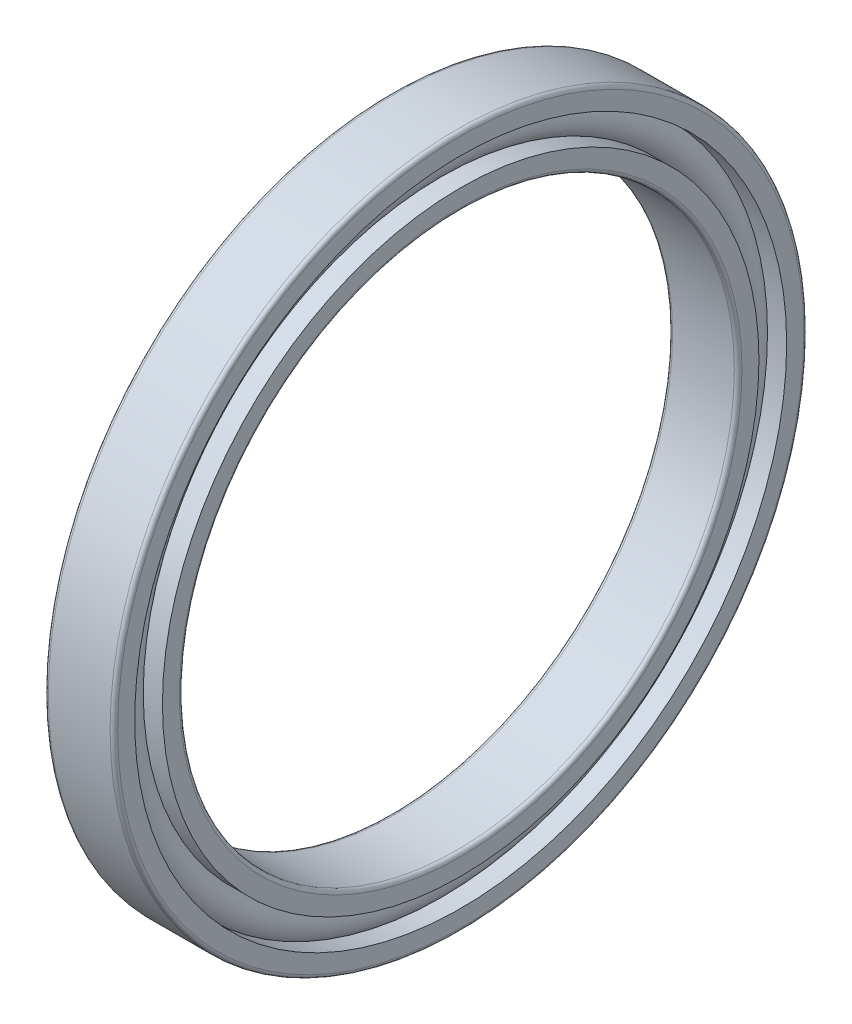
SolidWorks part; units mm, degrees
ref_plane "Plane1" through (0, 0, 0) normal (0, 0, 1) x (1, 0, 0)
ref_plane "Plane2" through (0, 0, 0) normal (0, 1, 0) x (1, 0, 0)
ref_plane "Plane3" through (0, 0, 0) normal (1, 0, 0) x (0, 0, -1)
other "Configuration Table"
sketch "Clipboard" plane through (0, 0, 0) normal (0, 0, 1) x (1, 0, 0)
  line L0 (-10, 0) -> (10, 0) construction
  line L1 (0, 0) -> (22.3471, -0.7804)
  line L2 (0, 0) -> (89.9452, 3.141)
  line L3 (0, 0) -> (22.3471, -0.7804)
  line L4 (0, 0) -> (-22.3573, -0.3902)
  dimension "BallCLRad" = 90
sketch "CagSpiSke" plane through (0, 0, 0) normal (0, 0, 1) x (1, 0, 0)
  line L0 (0.6, 89) -> (0.6, 91)
  line L1 (0.6, 91) -> (-0.6, 91)
  line L2 (-0.6, 91) -> (-0.6, 89)
  line L3 (-0.6, 89) -> (0.6, 89)
  line L4 (-20.6375, 0) -> (20.6375, 0) construction
  line L5 (0, 0) -> (0, 23.7692) construction
  dimension "OD" = 182
  dimension "ID" = 178
revolve "CageSpine" add sketch "CagSpiSke" angle 0.001 about L4 reverse direction yes
ref_axis "Axis1" through (-50, 0, 0) along (1, 0, 0)
sketch "CagBalSke" plane through (0, 0, 0) normal (0, 0, 1) x (1, 0, 0)
  line L0 (-6.6, 90) -> (6.6, 90)
  line L1 (-1.905, 90) -> (1.905, 90) construction
  line L2 (-10, 0) -> (10, 0) construction
  line L3 (0, 0) -> (0, 24) construction
  arc A0 (6.6, 90) -> (-6.6, 90) centre (0, 90) cw
  dimension "BallCLRad" = 90
revolve "CageBall" [suppressed] add sketch "CagBalSke" angle 360 about L1 reverse direction yes
pattern_circular "CageBalls" [suppressed] count 2 every 180 about axis through (-50, 0, 0) along (1, 0, 0)
sketch "CagTrmODSke" plane through (0, 0, 0) normal (0, 0, 1) x (1, 0, 0)
  line L0 (6.601, 91) -> (6.601, 96.601)
  line L1 (6.601, 96.601) -> (-6.601, 96.601)
  line L2 (-6.601, 96.601) -> (-6.601, 91)
  line L3 (-6.601, 91) -> (6.601, 91)
  line L4 (-20.6375, 0) -> (20.6375, 0) construction
  line L5 (0, 0) -> (0, 25) construction
  dimension "Width" = 13.202
  dimension "ID" = 182
  dimension "OD" = 193.202
revolve "CageTrimOD" [suppressed] cut sketch "CagTrmODSke" angle 360 about L4 reverse direction yes
sketch "CagTrmIDSke" plane through (0, 0, 0) normal (0, 0, 1) x (1, 0, 0)
  line L0 (6.601, 83.401) -> (6.601, 89)
  line L1 (6.601, 89) -> (-6.601, 89)
  line L2 (-6.601, 89) -> (-6.601, 83.401)
  line L3 (-6.601, 83.401) -> (6.601, 83.401)
  line L4 (-20.6375, 0) -> (20.6375, 0) construction
  line L5 (0, 0) -> (0, 25) construction
  dimension "Width" = 13.202
  dimension "ID" = 166.802
  dimension "OD" = 178
revolve "CageTrimID" [suppressed] cut sketch "CagTrmIDSke" angle 360 about L4 reverse direction yes
sketch "BalSimSke" plane through (0, 0, 0) normal (0, 0, 1) x (1, 0, 0)
  line L0 (-10, 0) -> (10, 0) construction
  line L1 (-10, 90) -> (10, 90) construction
  line L2 (0, 0) -> (0, 23) construction
  circle A0 centre (0, 90) radius 6
  dimension "BallCLRad" = 90
  dimension "Ball_diameter" = 12
revolve "BallsSimplified" add sketch "BalSimSke" angle 360 about L0
sketch "BalDetSke" plane through (0, 0, 0) normal (0, 0, 1) x (1, 0, 0)
  line L0 (-6, 90) -> (6, 90)
  line L1 (-1.905, 90) -> (1.905, 90) construction
  line L2 (0, 0) -> (0, 25) construction
  arc A0 (6, 90) -> (-6, 90) centre (0, 90) cw
  dimension "BallCLRad" = 90
  dimension "Ball_diameter" = 12
revolve "BallDetailed" [suppressed] add sketch "BalDetSke" angle 360 about L1 reverse direction yes
sketch "InnRacSke" plane through (0, 0, 0) normal (0, 0, 1) x (1, 0, 0)
  line L0 (-4.4385, 86) -> (-10, 86)
  line L1 (-10, 86) -> (-10, 81.1)
  line L2 (-8.9, 80) -> (8.9, 80)
  line L3 (10, 81.1) -> (10, 86)
  line L4 (10, 86) -> (4.4385, 86)
  line L5 (-20.6375, 0) -> (20.6375, 0) construction
  line L6 (0, 0) -> (0, 30) construction
  arc A0 (-10, 81.1) -> (-8.9, 80) centre (-8.9, 81.1) ccw
  arc A1 (8.9, 80) -> (10, 81.1) centre (8.9, 81.1) ccw
  arc A2 (4.4385, 86) -> (-4.4385, 86) centre (0, 90) cw
  dimension "BallCLRad" = 90
  dimension "Fillet_radius" = 1.1
  dimension "Ball_diameter" = 11.95
  dimension "ID" = 160
  dimension "OD" = 172
  dimension "Width" = 20
revolve "InnerRace" add sketch "InnRacSke" angle 360 about L5 reverse direction yes
sketch "OutRacSke" plane through (0, 0, 0) normal (0, 0, 1) x (1, 0, 0)
  line L0 (-4.4385, 94) -> (-10, 94)
  line L1 (-10, 94) -> (-10, 98.9)
  line L2 (-8.9, 100) -> (8.9, 100)
  line L3 (10, 98.9) -> (10, 94)
  line L4 (10, 94) -> (4.4385, 94)
  line L5 (-20.6375, 0) -> (20.6375, 0) construction
  line L6 (0, 0) -> (0, 30) construction
  arc A0 (-10, 98.9) -> (-8.9, 100) centre (-8.9, 98.9) cw
  arc A1 (8.9, 100) -> (10, 98.9) centre (8.9, 98.9) cw
  arc A2 (4.4385, 94) -> (-4.4385, 94) centre (0, 90) ccw
  dimension "BallCLRad" = 90
  dimension "Fillet_radius" = 1.1
  dimension "Ball_diameter" = 11.95
  dimension "Width" = 20
revolve "OuterRace" add sketch "OutRacSke" angle 360 about L5 reverse direction yes
pattern_circular "BallsDetailed" [suppressed] count 2 every 180 about axis through (-50, 0, 0) along (1, 0, 0)
equation "\"BallCLRad@Clipboard\" = ( \"OD@OutRacSke\" + \"ID@InnRacSke\" ) / 4"
equation "\"BallCLRad@BalSimSke\" = \"BallCLRad@Clipboard\""
equation "\"BallCLRad@BalDetSke\" = \"BallCLRad@Clipboard\""
equation "\"BallCLRad@InnRacSke\" = \"BallCLRad@Clipboard\""
equation "\"BallCLRad@OutRacSke\" = \"BallCLRad@Clipboard\""
equation "\"Ball_diameter@InnRacSke\" = \"Ball_diameter@BalDetSke\" - 0.05"
equation "\"Ball_diameter@OutRacSke\" = \"Ball_diameter@BalDetSke\" - 0.05"
equation "\"Ball_diameter@BalSimSke\" = \"Ball_diameter@BalDetSke\""
equation "\"Width@OutRacSke\" = \"Width@InnRacSke\""
equation "\"Fillet_radius@OutRacSke\" = \"Fillet_radius@InnRacSke\""
equation "\"Max_count@Clipboard\" = int( 3.14159265 / atn(( \"Ball_diameter@BalDetSke\" / 2) / sqr( \"BallCLRad@Clipboard\"  *  \"BallCLRad@Clipboard\" - ( \"Ball_diameter@BalDetSke\" / 2) *  ( \"Ball_diameter@BalDetSke\" / 2))))"
equation "\"Max_count@Clipboard\" = ((sgn( \"Max_count@Clipboard\" - \"Count@Clipboard\" )-1)*( \"Max_count@Clipboard\" - \"Count@Clipboard\" ))/-2+ \"Count@Clipboard\""
equation "\"Count@BallsDetailed\" = int( \"Show_count@Clipboard\" ) "
equation "\"Count@BallsDetailed\" = ((sgn( \"Count@BallsDetailed\" - \"Max_count@Clipboard\" )-1)*( \"Count@BallsDetailed\" - \"Max_count@Clipboard\" ))/-2+ \"Max_count@Clipboard\""
equation "\"Count@BallsDetailed\" = ((sgn( \"Count@BallsDetailed\" - \"Min_count@Clipboard\" )+1)*( \"Count@BallsDetailed\" - \"Min_count@Clipboard\"))/2 +\"Min_count@Clipboard\""
equation "\"Angle@BallsDetailed\" = 360.0 / \"Max_count@Clipboard\""
equation "\"BallCLRad@CagBalSke\" = \"BallCLRad@Clipboard\""
equation "\"Count@CageBalls\" = \"Count@BallsDetailed\""
equation "\"Angle@CageBalls\" = \"Angle@BallsDetailed\""
equation "\"Angle@CageSpine\" =  \"Angle@CageBalls\" * ( \"Count@CageBalls\" -1 + int( \"Count@CageBalls\" / \"Max_count@Clipboard\" ) )  + 0.001 -  int( \"Count@CageBalls\" / \"Max_count@Clipboard\" ) * 0.001"
equation "\"Angle@CageSpine\" =  \"Angle@CageSpine\" * int( \"Min_count@Clipboard\" / 2) + int(1 / \"Min_count@Clipboard\")  * 0.001"
equation "\"CageWallOD@CagBalSke\" =  \"Ball_diameter@BalDetSke\" * 1.1"
equation "\"Thickness@CagSpiSke\" =  \"Ball_diameter@BalDetSke\" * 0.1"
equation "\"OD@CagTrmODSke\" = \"BallCLRad@Clipboard\" * 2 + \"CageWallOD@CagBalSke\" + 0.002"
equation "\"ID@CagTrmODSke\" = \"BallCLRad@Clipboard\" * 2 + \"Ball_diameter@BalDetSke\" / 6"
equation "\"OD@CagTrmIDSke\" = \"BallCLRad@Clipboard\" * 2 - \"Ball_diameter@BalDetSke\" / 6"
equation "\"ID@CagTrmIDSke\" = \"BallCLRad@Clipboard\" * 2 - \"CageWallOD@CagBalSke\" + 0.002"
equation "\"OD@CagSpiSke\" = \"ID@CagTrmODSke\""
equation "\"ID@CagSpiSke\" = \"OD@CagTrmIDSke\""
equation "\"Width@CagTrmODSke\" = \"CageWallOD@CagBalSke\" + 0.002"
equation "\"Width@CagTrmIDSke\" = \"CageWallOD@CagBalSke\" + 0.002"
